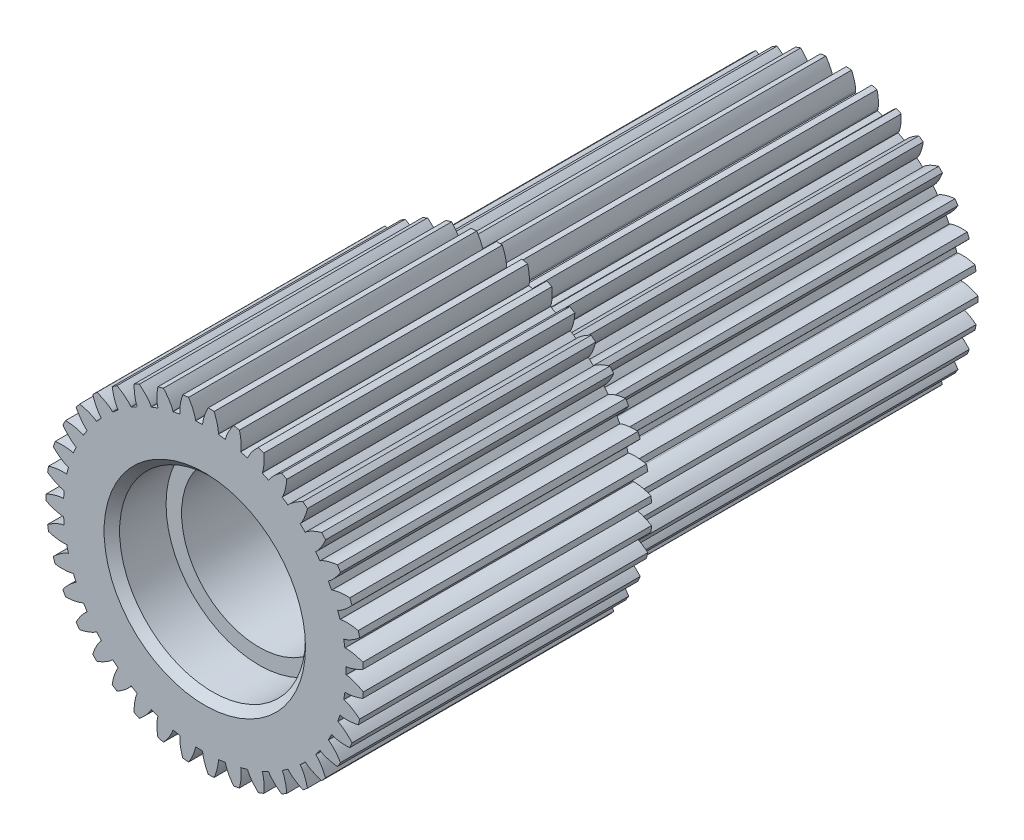
SolidWorks part; units mm, degrees
material "PLA"
ref_plane "Front Plane" through (0, 0, 0) normal (0, 0, 1) x (1, 0, 0)
ref_plane "Top Plane" through (0, 0, 0) normal (0, 1, 0) x (1, 0, 0)
ref_plane "Right Plane" through (0, 0, 0) normal (1, 0, 0) x (0, 0, -1)
sketch "Sketch1" plane through (0, 0, 0) normal (0, 0, 1) x (1, 0, 0)
  circle A0 centre (0, 0) radius 10.25
  dimension "D1" = 20.5
extrude "Boss-Extrude1" add sketch "Sketch1" along normal mid plane 18.6026
sketch "Sketch2" plane through (0, 0, 0) normal (0, 0, 1) x (1, 0, 0)
  line L0 (0, 0) -> (9.7469, 0.2474) construction
  line L1 (0, 0) -> (9.75, 0) construction
  line L2 (0, 0) -> (9.7469, -0.2474) construction
  line L3 (9.1566, -0.2324) -> (9.1221, -0.2315)
  line L4 (9.1591, 0.2324) -> (9.1221, 0.2315)
  circle A0 centre (0, 0) radius 9.75 construction
  circle A1 centre (0, 0) radius 9.162 construction
  circle A2 centre (0, 0) radius 9.125
  circle A3 centre (0, 0) radius 10.25 construction
  circle A4 centre (0, 0) radius 10.25
  spline S0 degree 4 poles (9.1591, 0.2324) (9.1622, 0.2326) (9.171, 0.2331) (9.1875, 0.2345) (9.2145, 0.2377) (9.2644, 0.2453) (9.3241, 0.2572) (9.3911, 0.2733) (9.4627, 0.2933) (9.5237, 0.3121) (9.5842, 0.3323) (9.6441, 0.3539) (9.7164, 0.3817) (9.8025, 0.4173) (9.9024, 0.4622) (10.0146, 0.517) (10.1278, 0.5769) (10.2382, 0.6392) (10.3484, 0.706) (10.4542, 0.7733) (10.5626, 0.847) (10.662, 0.917) (10.7718, 0.9997) (10.8598, 1.0676) (10.9742, 1.1617) (11.0411, 1.2185) (11.1188, 1.2866) (11.153, 1.3176) (11.174, 1.3366) knots 0 0 0 0 0 0.005377 0.015084 0.028532 0.04661 0.092111 0.119476 0.146842 0.174209 0.201575 0.228941 0.256307 0.307035 0.361767 0.4165 0.471232 0.525964 0.580697 0.635429 0.690161 0.744894 0.799626 0.854358 0.909091 0.954545 1 1 1 1 1 construction
  spline S1 degree 4 poles (9.1591, 0.2324) (9.1622, 0.2326) (9.171, 0.2331) (9.1875, 0.2345) (9.2145, 0.2377) (9.2644, 0.2453) (9.3241, 0.2572) (9.3911, 0.2733) (9.4627, 0.2933) (9.5237, 0.3121) (9.5842, 0.3323) (9.6441, 0.3539) (9.7164, 0.3817) (9.8025, 0.4173) (9.9024, 0.4622) (10.0146, 0.517) (10.1278, 0.5769) (10.2382, 0.6392) (10.3484, 0.706) (10.4542, 0.7733) (10.5626, 0.847) (10.662, 0.917) (10.7718, 0.9997) (10.8598, 1.0676) (10.9494, 1.1413) (10.9927, 1.1776) (11.0148, 1.1964) knots 0 0 0 0 0 0.005377 0.015084 0.028532 0.04661 0.092111 0.119476 0.146842 0.174209 0.201575 0.228941 0.256307 0.307035 0.361767 0.4165 0.471232 0.525964 0.580697 0.635429 0.690161 0.744894 0.799626 0.854358 0.909091 0.909091 0.909091 0.909091 0.909091
  spline S2 degree 4 poles (9.1566, -0.2324) (9.1597, -0.2325) (9.1685, -0.233) (9.1851, -0.2345) (9.212, -0.2376) (9.262, -0.2452) (9.3217, -0.2571) (9.3887, -0.2732) (9.4603, -0.2932) (9.5212, -0.312) (9.5817, -0.3323) (9.6417, -0.3539) (9.7139, -0.3817) (9.8001, -0.4173) (9.9, -0.4622) (10.0122, -0.5169) (10.1254, -0.5769) (10.2357, -0.6392) (10.346, -0.7059) (10.4517, -0.7732) (10.5602, -0.847) (10.6596, -0.917) (10.7693, -0.9996) (10.8574, -1.0676) (10.9717, -1.1616) (11.0387, -1.2185) (11.1164, -1.2865) (11.1505, -1.3175) (11.1715, -1.3366) knots 0 0 0 0 0 0.005377 0.015084 0.028532 0.04661 0.092111 0.119476 0.146842 0.174209 0.201575 0.228941 0.256307 0.307035 0.361767 0.4165 0.471232 0.525964 0.580697 0.635429 0.690161 0.744894 0.799626 0.854358 0.909091 0.954545 1 1 1 1 1 construction
  spline S3 degree 4 poles (9.1566, -0.2324) (9.1597, -0.2325) (9.1685, -0.233) (9.1851, -0.2345) (9.212, -0.2376) (9.262, -0.2452) (9.3217, -0.2571) (9.3887, -0.2732) (9.4603, -0.2932) (9.5212, -0.312) (9.5817, -0.3323) (9.6417, -0.3539) (9.7139, -0.3817) (9.8001, -0.4173) (9.9, -0.4622) (10.0122, -0.5169) (10.1254, -0.5769) (10.2357, -0.6392) (10.346, -0.7059) (10.4517, -0.7732) (10.5602, -0.847) (10.6596, -0.917) (10.7693, -0.9996) (10.8574, -1.0676) (10.9469, -1.1412) (10.9903, -1.1776) (11.0123, -1.1964) knots 0 0 0 0 0 0.005377 0.015084 0.028532 0.04661 0.092111 0.119476 0.146842 0.174209 0.201575 0.228941 0.256307 0.307035 0.361767 0.4165 0.471232 0.525964 0.580697 0.635429 0.690161 0.744894 0.799626 0.854358 0.909091 0.909091 0.909091 0.909091 0.909091
  dimension "D1" = 19.5
  dimension "D2" = 18.324
  dimension "D3" = 18.25
  dimension "D4" = 1.454
  dimension "D5" = 1.454
extrude "Cut-Extrude1" cut sketch "Sketch2" against normal through all both and the other way through all contours A2 A4 region at (9.7847, -0.0005, 0)
pattern_circular "CirPattern2" count 39 over 360 about axis through (0, 0, 9.3013) along (0, 0, -1) of "Cut-Extrude1"
sketch "Sketch3" plane through (0, 0, 9.3013) normal (0, 0, 1) x (1, 0, 0)
  circle A0 centre (0, 0) radius 5
  dimension "D1" = 10
sketch "Sketch4" plane through (0, 0, -9.3013) normal (0, 0, -1) x (-1, 0, 0)
  circle A0 centre (0, 0) radius 8.75
  dimension "D1" = 17.5
extrude "Boss-Extrude2" add sketch "Sketch4" along normal blind 22.5579
sketch "Sketch5" plane through (0, 0, -31.8592) normal (0, 0, -1) x (-1, 0, 0)
  line L0 (0, 0) -> (8.75, 0) construction
  line L1 (0, 0) -> (8.7453, 0.286) construction
  line L2 (0, 0) -> (8.7453, -0.286) construction
  line L3 (7.7282, 0.2528) -> (7.6209, 0.2493)
  line L4 (7.7282, -0.2528) -> (7.6209, -0.2493)
  circle A0 centre (0, 0) radius 7.7525 construction
  circle A1 centre (0, 0) radius 7.625
  arc A2 (8.7253, -0.6574) -> (8.7253, 0.6574) centre (0, 0) ccw
  spline S0 degree 4 poles (7.7282, 0.2528) (7.7309, 0.2529) (7.7383, 0.2534) (7.7612, 0.2556) (7.8061, 0.2621) (7.8613, 0.2731) (7.9243, 0.2888) (7.9848, 0.3061) (8.0362, 0.3224) (8.0873, 0.3399) (8.1379, 0.3586) (8.1989, 0.3825) (8.2716, 0.4132) (8.3558, 0.4518) (8.4504, 0.4988) (8.5458, 0.5502) (8.6388, 0.6036) (8.7317, 0.6608) (8.8207, 0.7184) (8.912, 0.7815) (8.9957, 0.8413) (9.088, 0.912) (9.1621, 0.97) (9.2583, 1.0503) (9.3146, 1.0988) (9.3799, 1.1568) (9.4086, 1.1833) (9.4263, 1.1996) knots 0 0 0 0 0 0.005377 0.015084 0.04661 0.092111 0.119476 0.146842 0.174209 0.201575 0.228941 0.256307 0.307035 0.361767 0.4165 0.471232 0.525964 0.580697 0.635429 0.690161 0.744894 0.799626 0.854358 0.909091 0.954545 1 1 1 1 1 construction
  spline S1 degree 4 poles (7.7282, 0.2528) (7.7309, 0.2529) (7.7383, 0.2534) (7.7612, 0.2556) (7.8061, 0.2621) (7.8613, 0.2731) (7.9243, 0.2888) (7.9848, 0.3061) (8.0362, 0.3224) (8.0873, 0.3399) (8.1379, 0.3586) (8.1989, 0.3825) (8.2716, 0.4132) (8.3558, 0.4518) (8.4504, 0.4988) (8.5458, 0.5502) (8.6388, 0.6036) (8.7317, 0.6608) (8.8207, 0.7184) (8.912, 0.7815) (8.9957, 0.8413) (9.088, 0.912) (9.1621, 0.97) (9.2374, 1.0329) (9.2739, 1.0639) (9.2925, 1.0799) knots 0 0 0 0 0 0.005377 0.015084 0.04661 0.092111 0.119476 0.146842 0.174209 0.201575 0.228941 0.256307 0.307035 0.361767 0.4165 0.471232 0.525964 0.580697 0.635429 0.690161 0.744894 0.799626 0.854358 0.909091 0.909091 0.909091 0.909091 0.909091
  spline S2 degree 4 poles (7.7282, -0.2528) (7.7309, -0.2529) (7.7383, -0.2534) (7.7612, -0.2556) (7.8061, -0.2621) (7.8613, -0.2731) (7.9243, -0.2888) (7.9848, -0.3061) (8.0362, -0.3224) (8.0873, -0.3399) (8.1379, -0.3586) (8.1989, -0.3825) (8.2716, -0.4132) (8.3558, -0.4518) (8.4504, -0.4988) (8.5458, -0.5502) (8.6388, -0.6036) (8.7317, -0.6608) (8.8207, -0.7184) (8.912, -0.7815) (8.9957, -0.8413) (9.088, -0.912) (9.1621, -0.97) (9.2583, -1.0503) (9.3146, -1.0988) (9.3799, -1.1568) (9.4086, -1.1833) (9.4263, -1.1996) knots 0 0 0 0 0 0.005377 0.015084 0.04661 0.092111 0.119476 0.146842 0.174209 0.201575 0.228941 0.256307 0.307035 0.361767 0.4165 0.471232 0.525964 0.580697 0.635429 0.690161 0.744894 0.799626 0.854358 0.909091 0.954545 1 1 1 1 1 construction
  spline S3 degree 4 poles (7.7282, -0.2528) (7.7309, -0.2529) (7.7383, -0.2534) (7.7612, -0.2556) (7.8061, -0.2621) (7.8613, -0.2731) (7.9243, -0.2888) (7.9848, -0.3061) (8.0362, -0.3224) (8.0873, -0.3399) (8.1379, -0.3586) (8.1989, -0.3825) (8.2716, -0.4132) (8.3558, -0.4518) (8.4504, -0.4988) (8.5458, -0.5502) (8.6388, -0.6036) (8.7317, -0.6608) (8.8207, -0.7184) (8.912, -0.7815) (8.9957, -0.8413) (9.088, -0.912) (9.1621, -0.97) (9.2374, -1.0329) (9.2739, -1.0639) (9.2925, -1.0799) knots 0 0 0 0 0 0.005377 0.015084 0.04661 0.092111 0.119476 0.146842 0.174209 0.201575 0.228941 0.256307 0.307035 0.361767 0.4165 0.471232 0.525964 0.580697 0.635429 0.690161 0.744894 0.799626 0.854358 0.909091 0.909091 0.909091 0.909091 0.909091
  dimension "D2" = 15.25
  dimension "D3" = 17.5
  dimension "D1" = 15.5049
  dimension "D4" = 1.873
  dimension "D5" = 1.873
extrude "Cut-Extrude2" cut sketch "Sketch5" against normal up to surface (22.5579 mm away) contours A2 A1 region at (-8.2828, 0, -31.8592) up to face at (8.75, 0, -9.3013)
pattern_circular "CirPattern3" count 33 over 360 about axis through (0, 0, -31.8592) along (0, 0, 1) of "Cut-Extrude2"
extrude "Cut-Extrude3" cut sketch "Sketch3" against normal through all contours A0
sketch "Sketch7" plane through (0, 0, -31.8592) normal (0, 0, -1) x (-1, 0, 0)
  circle A0 centre (0, 0) radius 6
  dimension "D1" = 12
extrude "Cut-Extrude4" cut sketch "Sketch7" against normal blind 3.5
ref_plane "Plane1" through (0, 0, -11.279) normal (0, 0, -1) x (-1, 0, 0)
mirror "Mirror1" about plane through (0, 0, -11.279) normal (0, 0, -1) of "Cut-Extrude4"
chamfer "Chamfer1" distance 0.5 angle 45 2 edges at (-6, 0, 9.3013) (-6, 0, -31.8592)
equation "\"module\" = 0.5"
equation "\"pressure angle\" = 20.0"
equation "\"h_a\" = 0.5"
equation "\"h_b\" = 0.625"
equation "\"clr_tip_root\" = 0.125"
equation "\"D1@Sketch1\" = \"dp_p_b\" + 2 * \"h_a\""
equation "\"D1@Boss-Extrude1\" = \"fw_p_b\""
equation "\"D1@Sketch2\" = \"dp_p_b\""
equation "\"D2@Sketch2\"= \"db_p_b\""
equation "\"D3@Sketch2\" = \"dp_p_b\" - 2 * \"h_b\""
equation "\"Nr_s\" = 138"
equation "\"pressure_angle\" = 20.0"
equation "\"h_f\" = 0.625"
equation "\"dp_r_s\" = 69.0"
equation "\"bearing_ID\" = 60"
equation "\"bearing_OD\" = 78"
equation "\"bearing_height\" = 10"
equation "\"clearance_planet\" = 1.5"
equation "\"case_dist\" = 6.5"
equation "\"Motor_case_OD_max\" = 96.5"
equation "\"case_mounting_PCD\" = 89.0"
equation "\"bearing mount thickness\" = 8"
equation "\"case_mounting_hole_dia\" = 3"
equation "\"output_mounting_PCD\" = 86"
equation "\"output_mounting_hole_dia\" = 4"
equation "\"clearance_case_mount_holes_shell_thickness\" = 1"
equation "\"motor_case_OD_base\" = 87.0"
equation "\"sec_carrier_thickness\" = 5"
equation "\"sun_coupler_hub_thickness\" = 4"
equation "\"clearance_sun_coupler_sec_carrier\" = 1.5"
equation "\"clearance_motor_and_case\" = 5.0"
equation "\"motor_OD\" = 72"
equation "\"Motor_case_thickness\" = 2.5"
equation "\"Motor_case_ID\" = 82.0"
equation "\"case_mounting_hole_shift\" = 1.0"
equation "\"output_mounting_nut_wrench_size\" = 7"
equation "\"output_mounting_nut_thickness\" = 3.2"
equation "\"case_mounting_hole_allen_socket_dia\" = 5.5"
equation "\"output_mounting_nut_depth\" = 3"
equation "\"case_mounting_bolt_depth\" = 4.5"
equation "\"Ns\" = 66"
equation "\"ring_radial_thickness\" = 5"
equation "\"ring_to_chamfer_clearance\" = 1.5"
equation "\"Motor_case_OD_base_to_chamfer\" = 5"
equation "\"pattern_offset_from_motor_case_OD_base\" = 3"
equation "\"pattern_bulge_dia\" = 3"
equation "\"pattern_num_bulge\" = 18"
equation "\"pattern_depth\" = 2"
equation "\"motor_height\" = 27"
equation "\"case_mounting_wrench_size\" = 5.5"
equation "\"case_mounting_nut_clearance\" = 2"
equation "\"base_plate_thickness\" = 4"
equation "\"case_mounting_nut_thickness\" = 2.4"
equation "\"case_mounting_surface_height\" = 4"
equation "\"motor_mount_hole_PCD\" = 32"
equation "\"motor_mount_hole_dia\" = 4"
equation "\"motor_mount_hole_num\" = 4"
equation "\"central_hole_offset_from_motor_mount_PCD\" = 5"
equation "\"wire_slot_dist_from_center\" = 26"
equation "\"wire_slot_length\" = 10"
equation "\"wire_slot_radius\" = 2.5"
equation "\"driver_upper_holes_dist_from_center\" = 29"
equation "\"driver_lower_holes_dist_from_center\" = 13"
equation "\"driver_side_holes_dist_from_center\" = 22.5"
equation "\"driver_mount_holes_dia\" = 3"
equation "\"driver_mount_inserts_OD\" = 4.8"
equation "\"driver_mount_thickness\" = 1.5"
equation "\"driver_mount_height\" = 6"
equation "\"air_flow_hole_offset\" = 3"
equation "\"num_planet\" = 6"
equation "\"planet_pin_bolt_dia\" = 5"
equation "\"planet_pin_socket_head_dia\" = 8.5"
equation "\"carrier_PCD\" = 52.5"
equation "\"planet_shaft_dia\" = 8"
equation "\"planet_shaft_step_offset\" = 1"
equation "\"carrier_trapezoidal_support_sun_offset\" = 5"
equation "\"carrier_trapezoidal_support_hole_PCD_offset_bearing_ID\" = 4"
equation "\"carrier_trapezoidal_support_hole_dia\" = 3"
equation "\"carrier_trapezoidal_support_hole_socket_head_dia\" = 5.5"
equation "\"carrier_bearing_step_width\" = 1.5"
equation "\"standard_clearance_1_5mm\" = 1.5"
equation "\"standard_fillet_1_5mm\" = 1.5"
equation "\"sun_shaft_bearing_OD\" = 16"
equation "\"sun_shaft_bearing_width\" = 5"
equation "\"standard_bearing_insertion_chamfer\" = 0.5"
equation "\"carrier_trapezoidal_support_hole_wrench_size\" = 5.5"
equation "\"planet_pin_bolt_wrench_size\" = 8"
equation "\"planet_bearing_OD\" = 12"
equation "\"planet_bearing_width\" = 3.5"
equation "\"planet_bore\" = 10"
equation "\"D1@Sketch3\"=\"planet_bore\""
equation "\"Np_b\" = 39"
equation "\"dp_s\" = 33.0"
equation "\"db_s\" = 31.00985648593498"
equation "\"fw_s_calc\" = 1.5726146484026726"
equation "\"alpha_s\" = 0.8539582918412449"
equation "\"beta_s\" = 1.0193561435902372"
equation "\"dp_p_b\" = 19.5"
equation "\"db_p_b\" = 18.324006105325214"
equation "\"fw_p_s\" = 22.55792585723615"
equation "\"alpha_p_b\" = 0.8539582918412414"
equation "\"beta_p_b\" = 2.907468031702132"
equation "\"motor_output_hole_PCD\" = 22"
equation "\"motor_output_hole_dia\" = 3"
equation "\"motor_output_hole_num\" = 4"
equation "\"sun_shaft_bearing_ID\" = 8"
equation "\"sun_hub_dia\" = 28.0"
equation "\"sun_central_bolt_dia\" = 5"
equation "\"sun_central_bolt_socket_head_dia\" = 8.5"
equation "\"fw_s_used\" = 48.660536742005725"
equation "\"motor_output_hole_CSK_OD\" = 6"
equation "\"motor_output_hole_CSK_head_height\" = 1.5"
equation "\"bearing_retainer_thickness\" = 2"
equation "\"Np_s\" = 33"
equation "\"fw_p_b\" = 18.602610884769575"
equation "\"dp_p_s\" = 16.5"
equation "\"db_p_s\" = 15.50492824296749"
equation "\"alpha_p_s\" = 0.8539582918412449"
equation "\"beta_p_s\" = 3.7466288708629643"
equation "\"D1@Sketch4\"=\"dp_p_s\" + 2 * \"h_a\""
equation "\"D1@Boss-Extrude2\"=\"fw_p_s\""
equation "\"D2@Sketch5\"=\"dp_p_s\" - 2 * \"h_b\""
equation "\"D3@Sketch5\"=\"dp_p_s\"+2 * \"h_a\" "
equation "\"D1@Sketch5\"=\"db_p_s\""
equation "\"D1@CirPattern3\"=\"Np_s\""
equation "\"D4@Sketch5\"=\"beta_p_s\"/2"
equation "\"D5@Sketch5\"=\"beta_p_s\"/2"
equation "\"D4@Sketch2\"=\"beta_p_b\"/2"
equation "\"D5@Sketch2\"=\"beta_p_b\"/2"
equation "\"D1@Sketch7\"=\"planet_bearing_OD\""
equation "\"D1@Cut-Extrude4\"=\"planet_bearing_width\""
equation "\"D1@Chamfer1\"=\"standard_bearing_insertion_chamfer\""
equation "\"D1@CirPattern2\"=\"Np_b\""
equation "\"Nr_b\" = 144"
equation "\"dp_r_b\" = 72.0"
equation "\"db_r_b\" = 67.65786869658541"
equation "\"fw_r_b\" = 18.602610884769575"
equation "\"alpha_r_b\" = 0.8539582918412343"
equation "\"beta_r_b\" = 2.9579165836824686"
equation "\"ring_OD_b\" = 82.0"
equation "\"Fillet10\"= IIF ( \"ring_OD_b\" > ( \"bearing_OD\" + 2 * \"bearing mount thickness\" ) , \"suppressed\" , \"unsuppressed\" )"
equation "\"Fillet11\"= IIF ( \"ring_OD_b\" < ( \"bearing_OD\" + 2 * \"bearing mount thickness\" ) , \"suppressed\" , \"unsuppressed\" )"
equation "\"clr_tip_root_s\" = 0.125"
equation "\"db_r_s\" = 64.83879083422768"
equation "\"fw_r_s\" = 21.05792585723615"
equation "\"alpha_r_s\" = 0.8539582918412485"
equation "\"beta_r_s\" = 3.0122644097694535"
equation "\"small_ring_case_thickness\" = 4"
equation "\"carrier_thickness\" = 4"
equation "\"small_ring_output_wall_thickness\" = 5"
equation "\"small_ring_output_wall_to_bearing_shaft_attachement_hole_dia\" = 4"
equation "\"small_ring_output_wall_to_bearing_shaft_attachement_hole_depth\" = 6.5"
equation "\"small_ring_output_wall_to_bearing_shaft_attachement_nut_wrench\" = 7"
equation "\"small_ring_output_wall_to_bearing_shaft_attachement_nut_thickness\" = 3.2"
equation "\"small_ring_output_wall_to_bearing_shaft_attachement_hole_pcd\" = 12"
equation "\"small_ring_output_wall_to_bearing_shaft_attachement_hole_num\" = 3"
equation "\"small_ring_output_wall_to_bearing_shaft_attachement_hole_CSK_OD\" = 8"
equation "\"small_ring_output_wall_to_bearing_shaft_attachement_hole_CSK_head_height\" = 2.0"
equation "\"carrier_small_ring_inner_bearing_ID\" = 20"
equation "\"carrier_small_ring_inner_bearing_OD\" = 32"
equation "\"carrier_small_ring_inner_bearing_height\" = 7"
equation "\"carrier_small_ring_inner_bearing_flap\" = 2"
equation "\"gear_casing_big_ring_to_bearing_dist\" = 31.55792585723615"
equation "\"gear_casing_thickness\" = 4"
